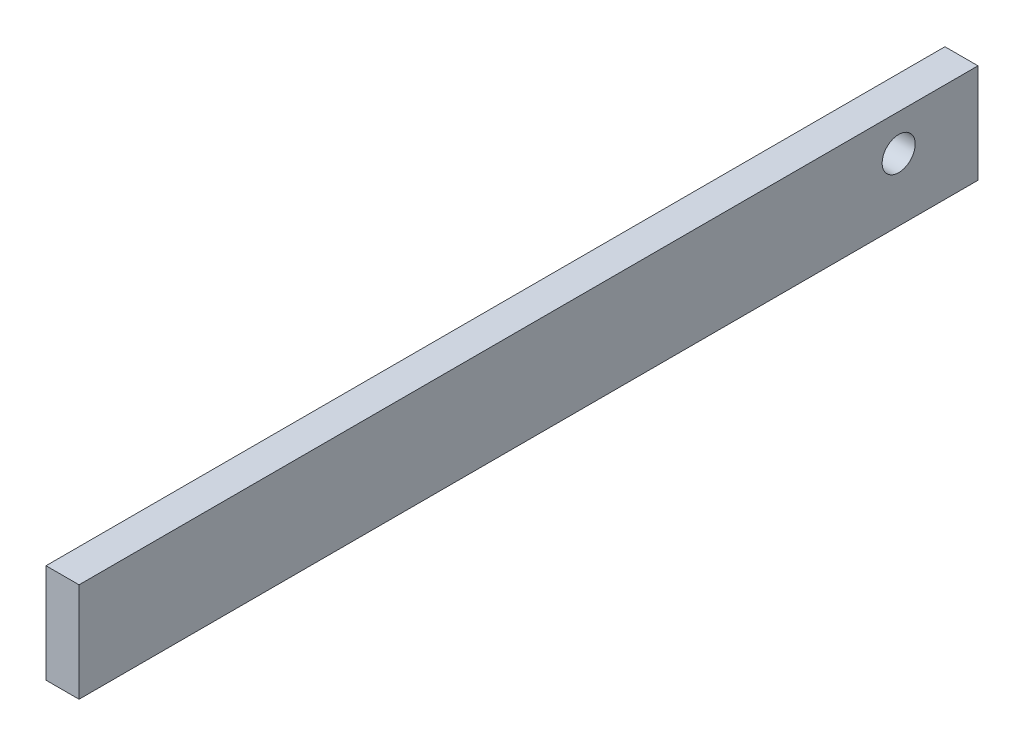
SolidWorks part; units mm, degrees
ref_plane "Front Plane" through (0, 0, 0) normal (0, 0, 1) x (1, 0, 0)
ref_plane "Top Plane" through (0, 0, 0) normal (0, 1, 0) x (1, 0, 0)
ref_plane "Right Plane" through (0, 0, 0) normal (1, 0, 0) x (0, 0, -1)
sketch "Sketch1" plane through (0, 0, 0) normal (0, 0, 1) x (1, 0, 0)
  line L0 (0, 0) -> (-12.7, 0)
  line L1 (-12.7, 0) -> (-12.7, 19.05)
  line L2 (-12.7, 19.05) -> (-6.35, 19.05)
  line L3 (-6.35, 19.05) -> (-6.35, 6.35)
  line L4 (-6.35, 6.35) -> (0, 6.35)
  line L5 (0, 6.35) -> (0, 0)
  dimension "D1" = 6.35
  dimension "D2" = 6.35
  dimension "D3" = 6.35
  dimension "D4" = 12.7
extrude "Boss-Extrude1" add sketch "Sketch1" against normal blind 172.72
sketch "Sketch2" plane through (-12.7, 0, 0) normal (-1, 0, 0) x (0, 0, 1)
  line L0 (-172.72, 0) -> (0, 0) construction
  line L1 (-172.72, 19.05) -> (-172.72, 0) construction
  circle A0 centre (-157.48, 12.065) radius 3.175
  point P4 (0, 0)
  dimension "D1" = 6.35
  dimension "D2" = 12.065
  dimension "D3" = 15.24
extrude "Cut-Extrude1" cut sketch "Sketch2" against normal up to next
sketch "Sketch3" plane through (0, 19.05, 0) normal (0, 1, 0) x (1, 0, 0)
  line L0 (-9.525, 172.72) -> (-9.525, 0) construction
  line L1 (-6.35, 172.72) -> (-12.7, 172.72) construction
  line L2 (-6.35, 0) -> (-12.7, 0) construction
  circle A0 centre (-9.525, 6.35) radius 2.54
  circle A1 centre (-9.525, 166.37) radius 2.54
  dimension "D1" = 5.08
  dimension "D3" = 6.35
  dimension "D2" = 6.35
sketch "Sketch4" plane through (0, 0, 0) normal (0, -1, 0) x (1, 0, 0)
  line L0 (-9.525, 0) -> (-9.525, -172.72) construction
  line L1 (-12.7, 0) -> (0, 0) construction
  line L2 (-12.7, -172.72) -> (0, -172.72) construction
  line L3 (0, -172.72) -> (0, 0) construction
  circle A0 centre (-9.525, -166.37) radius 2.54
  circle A1 centre (-9.525, -6.35) radius 2.54
  dimension "D2" = 5.08
  dimension "D1" = 9.525
  dimension "D3" = 6.35
  dimension "D4" = 6.35
sketch "Sketch5" plane through (0, 0, -172.72) normal (0, 0, -1) x (-1, 0, 0)
  line L1 (6.35, 6.35) -> (0, 6.35)
  line L2 (6.35, 6.35) -> (6.35, 0)
  line L3 (6.35, 0) -> (0, 0)
  line L4 (0, 6.35) -> (0, 0)
extrude "Cut-Extrude4" cut sketch "Sketch5" against normal blind 345.44
